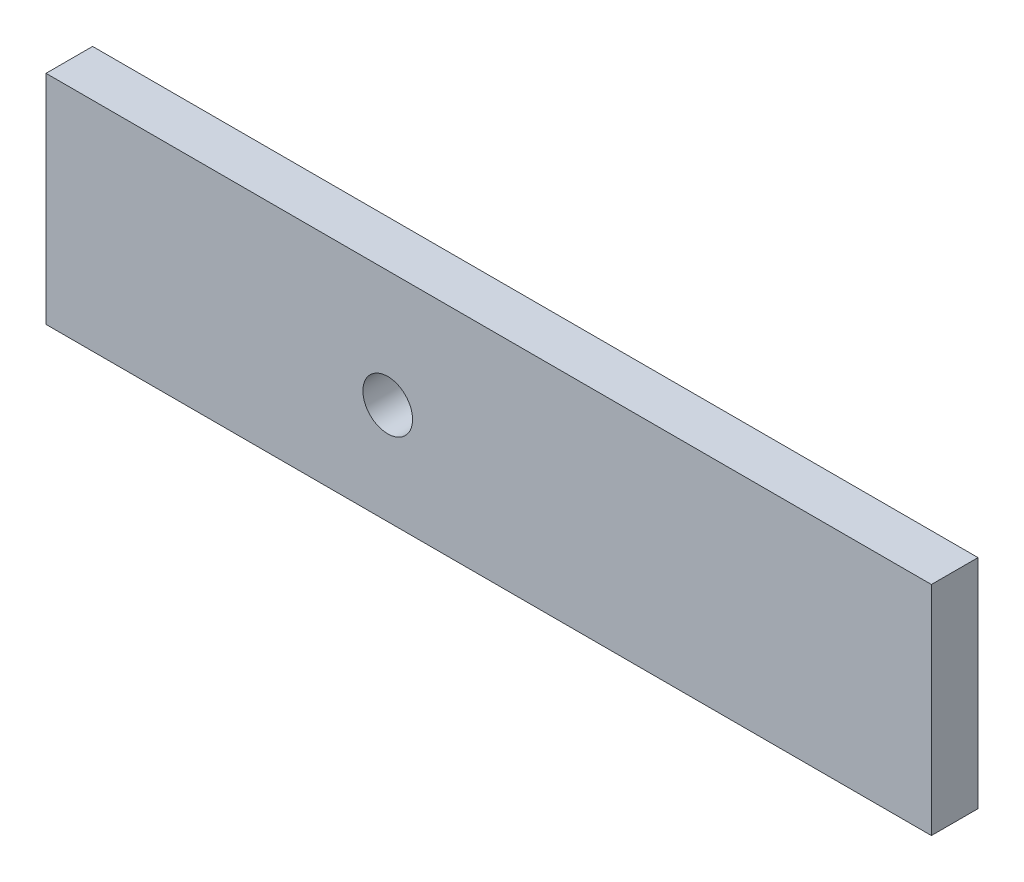
SolidWorks part; units mm, degrees
ref_plane "前视基准面" through (0, 0, 0) normal (0, 0, 1) x (1, 0, 0)
ref_plane "上视基准面" through (0, 0, 0) normal (0, 1, 0) x (1, 0, 0)
ref_plane "右视基准面" through (0, 0, 0) normal (1, 0, 0) x (0, 0, -1)
sketch "草图1" plane through (0, 0, 0) normal (0, 0, 1) x (1, 0, 0)
  line L0 (18.1, 0.8) -> (-10.4, 0.8)
  line L1 (-8.4, 0.8) -> (-1.9, 0.8) construction
  line L2 (18.1, 7.8) -> (18.1, 0.8)
  line L3 (-10.4, 0.8) -> (-10.4, 7.8)
  line L5 (-10.4, 7.8) -> (18.1, 7.8)
  line L6 (-10.4, 0) -> (-10.4, -1.5) construction
  line L7 (13.1, 0.8) -> (13.1, 5.8) construction
  circle A0 centre (0.6, 3.3) radius 1.75 construction
  circle A1 centre (0.6, 3.3) radius 1.75 construction
  circle A2 centre (0.6, 4.05) radius 1 construction
  dimension "D1" = 2
  dimension "D2" = 7
  dimension "D3" = 5
extrude "base" add sketch "草图1" along normal blind 1.5 contours L5 L2 L0 L3
sketch "草图4" plane through (0, 0, 0) normal (0, 0, -1) x (-1, 0, 0)
  circle A0 centre (-11.1, 3.3) radius 0.85 construction
  circle A1 centre (-11.1, 3.3) radius 0.85 construction
  circle A2 centre (-0.6, 3.3) radius 1.75 construction
  circle A3 centre (-0.6, 3.3) radius 1.75 construction
  circle A4 centre (-11.1, 3.3) radius 0.725
  dimension "D1" = 1.45
extrude "axis" add sketch "草图4" along normal offset from surface (1.9 mm away) 0.4 offset beyond the face yes
sketch "草图5" plane through (0, 0, 0) normal (0, 0, -1) x (-1, 0, 0)
  circle A0 centre (-0.6, 3.3) radius 1.75 construction
  circle A1 centre (-0.6, 3.3) radius 1.75 construction
  circle A2 centre (-0.6, 4.05) radius 1 construction
  dimension "D1" = 2
hole_wizard "M2 螺纹孔的螺纹孔钻头1" positions "3D草图1" profile "草图6" hole size "M2" standard "ISO" end condition up to next
sketch3d "3D草图1"
  point P0 (0.6, 4.05, 0)
sketch "草图6" plane through (0.6, 4.05, 0) normal (1, 0, 0) x (0, 1, 0)
  line L0 (0, 0) -> (0, 1.5)
  line L1 (0, 1.5) -> (0.8, 1.5)
  line L2 (0.8, 1.5) -> (0.8, 0)
  line L5 (0.8, 0) -> (0, 0)
  line L11 (0, -6.35) -> (0, 107.95) construction
  dimension "通孔孔直径" = 1.6
  dimension "通孔孔深度" = 1.5
